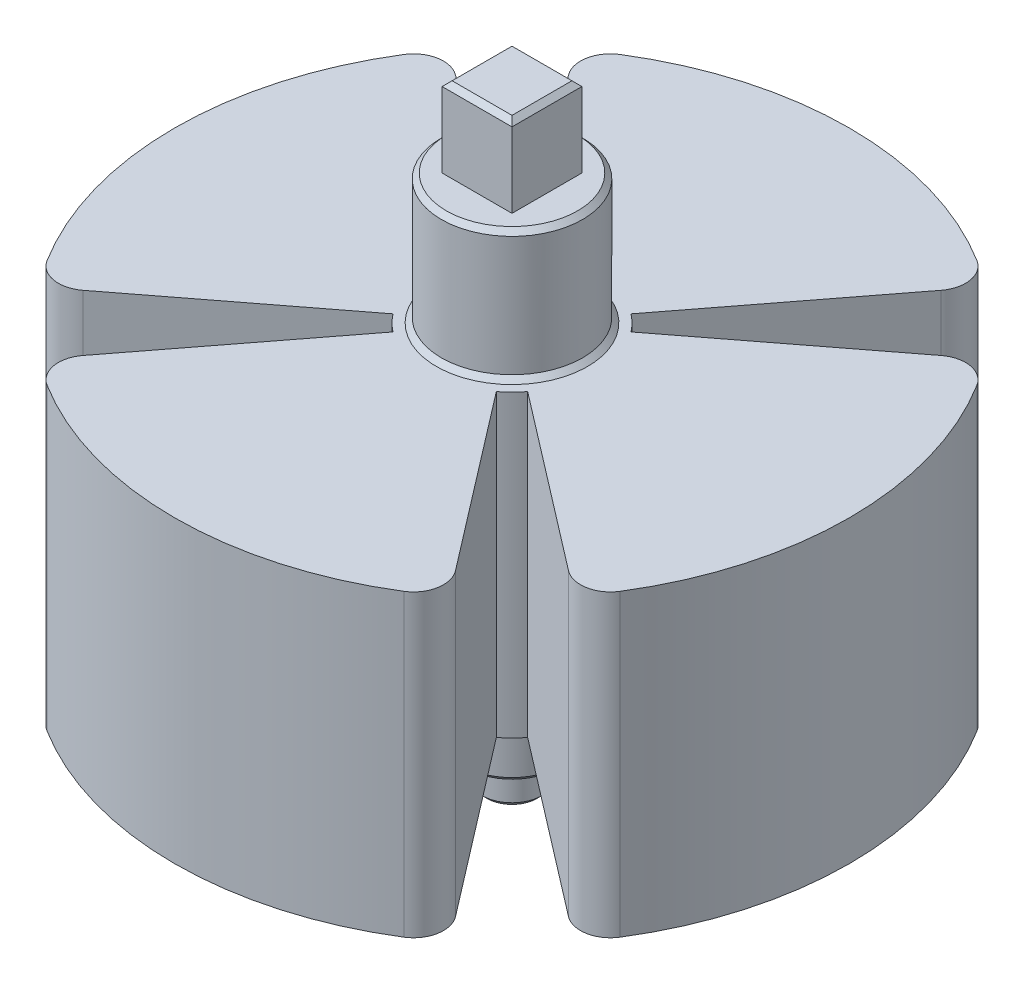
SolidWorks part; units mm, degrees
material "2024-O"
ref_plane "Front Plane" through (0, 0, 0) normal (0, 0, 1) x (1, 0, 0)
ref_plane "Top Plane" through (0, 0, 0) normal (0, 1, 0) x (1, 0, 0)
ref_plane "Right Plane" through (0, 0, 0) normal (1, 0, 0) x (0, 0, -1)
sketch "Sketch1" plane through (0, 0, 0) normal (0, 1, 0) x (1, 0, 0)
  line L0 (0, -1000) -> (0, 49000) construction
  line L1 (-9.4434, 18.6449) -> (1.2277, -4.2394)
  line L2 (10.4722, 2.3667) -> (15.7663, 13.7199)
  line L3 (18.6449, 9.4434) -> (-4.2394, -1.2277)
  line L4 (2.3667, -10.4722) -> (13.7199, -15.7663)
  line L5 (9.4434, -18.6449) -> (-1.2277, 4.2394)
  line L6 (-10.4722, -2.3667) -> (-15.7663, -13.7199)
  line L7 (-18.6449, -9.4434) -> (4.2394, 1.2277)
  line L8 (-2.3667, 10.4722) -> (-13.7199, 15.7663)
  line L10 (-1.75, 1.75) -> (1.75, 1.75)
  line L11 (-1.75, 1.75) -> (-1.75, -1.75)
  line L12 (-1.75, -1.75) -> (1.75, -1.75)
  line L13 (1.75, 1.75) -> (1.75, -1.75)
  line L14 (-1.75, 1.75) -> (1.75, -1.75) construction
  line L15 (-1.75, -1.75) -> (1.75, 1.75) construction
  circle A0 centre (0, 0) radius 20.9 construction
  arc A1 (-13.7199, 15.7663) -> (-18.6449, -9.4434) centre (0, 0) ccw
  circle A2 centre (0, 0) radius 17.15
  arc A3 (1.2277, -4.2394) -> (10.4722, 2.3667) centre (0, 7.25) ccw
  arc A4 (-4.2394, -1.2277) -> (2.3667, -10.4722) centre (7.25, 0) ccw
  arc A5 (-1.2277, 4.2394) -> (-10.4722, -2.3667) centre (0, -7.25) ccw
  arc A6 (4.2394, 1.2277) -> (-2.3667, 10.4722) centre (-7.25, 0) ccw
  arc A7 (-15.7663, -13.7199) -> (9.4434, -18.6449) centre (0, 0) ccw
  arc A8 (13.7199, -15.7663) -> (18.6449, 9.4434) centre (0, 0) ccw
  arc A9 (15.7663, 13.7199) -> (-9.4434, 18.6449) centre (0, 0) ccw
  circle A10 centre (0, 0) radius 3.5355
  point P29 (0, 0)
  dimension "D1" = 41.8
  dimension "D4" = 7.25
  dimension "D7" = 3.75
  dimension "D8" = 7.0711
  dimension "D2" = 25
  dimension "D3" = 25
  dimension "D6" = 3.5
  dimension "D5" = 4
extrude "Boss-Extrude1" add sketch "Sketch1" against normal blind 6.5 contours A10
extrude "Boss-Extrude2" add sketch "Sketch1<6>" along normal blind 4 contours L10 L13 L12 L11
sketch "Sketch1<6>" plane through (0, 0, 0) normal (0, 1, 0) x (1, 0, 0) same geometry as "Sketch1"
sketch "Sketch4" plane through (0, -6.5, 0) normal (0, -1, 0) x (1, 0, 0)
  circle A0 centre (0, 0) radius 4.25
  dimension "D1" = 8.5
extrude "Boss-Extrude5" add sketch "Sketch4" along normal blind 15 contours A0
sketch "Sketch2" plane through (0, -21.5, 0) normal (0, -1, 0) x (1, 0, 0)
  circle A0 centre (0, 0) radius 2.5
extrude "Boss-Extrude3" add sketch "Sketch2" along normal blind 3.2
sketch "Sketch3" plane through (0, -24.7, 0) normal (0, -1, 0) x (1, 0, 0)
  circle A0 centre (0, 0) radius 1.5
  dimension "D1" = 3
extrude "Boss-Extrude4" add sketch "Sketch3" along normal blind 1.8
sketch "Sketch5" plane through (0, -6.5, 0) normal (0, 1, 0) x (1, 0, 0)
  line L0 (-9.3303, 12.1595) -> (-1.19, 1.5509)
  line L1 (1.19, 1.5509) -> (9.3303, 12.1595)
  line L2 (0, -201000) -> (0, 249000) construction
  line L3 (12.1595, 9.3303) -> (1.5509, 1.19)
  line L4 (1.5509, -1.19) -> (12.1595, -9.3303)
  line L5 (9.3303, -12.1595) -> (1.19, -1.5509)
  line L6 (-1.19, -1.5509) -> (-9.3303, -12.1595)
  line L7 (-12.1595, -9.3303) -> (-1.5509, -1.19)
  line L8 (-1.5509, 1.19) -> (-12.1595, 9.3303)
  arc A0 (8.9332, 14.346) -> (-8.9332, 14.346) centre (0, 0) ccw
  circle A1 centre (0, 0) radius 17.15 construction
  arc A2 (9.3303, 12.1595) -> (8.9332, 14.346) centre (8.1403, 13.0727) ccw
  arc A3 (-9.3303, 12.1595) -> (-8.9332, 14.346) centre (-8.1403, 13.0727) cw
  arc A4 (-1.19, 1.5509) -> (1.19, 1.5509) centre (0, 2.464) ccw
  arc A5 (14.346, -8.9332) -> (14.346, 8.9332) centre (0, 0) ccw
  arc A6 (12.1595, -9.3303) -> (14.346, -8.9332) centre (13.0727, -8.1403) ccw
  arc A7 (12.1595, 9.3303) -> (14.346, 8.9332) centre (13.0727, 8.1403) cw
  arc A8 (1.5509, 1.19) -> (1.5509, -1.19) centre (2.464, 0) ccw
  arc A9 (-8.9332, -14.346) -> (8.9332, -14.346) centre (0, 0) ccw
  arc A10 (-9.3303, -12.1595) -> (-8.9332, -14.346) centre (-8.1403, -13.0727) ccw
  arc A11 (9.3303, -12.1595) -> (8.9332, -14.346) centre (8.1403, -13.0727) cw
  arc A12 (1.19, -1.5509) -> (-1.19, -1.5509) centre (0, -2.464) ccw
  arc A13 (-14.346, 8.9332) -> (-14.346, -8.9332) centre (0, 0) ccw
  arc A14 (-12.1595, 9.3303) -> (-14.346, 8.9332) centre (-13.0727, 8.1403) ccw
  arc A15 (-12.1595, -9.3303) -> (-14.346, -8.9332) centre (-13.0727, -8.1403) cw
  arc A16 (-1.5509, -1.19) -> (-1.5509, 1.19) centre (-2.464, 0) ccw
  point P45 (0, 0)
  dimension "D4" = 1.5
  dimension "D5" = 1.5
  dimension "D1" = 0.25
  dimension "D2" = 37.5
  dimension "D3" = 37.5
  dimension "D6" = 4
extrude "Boss-Extrude6" add sketch "Sketch5" against normal up to surface (15 mm away) up to face at (0, -21.5, -2.5)
chamfer "Chamfer1" distance 0.25 angle 45 10 edges at (0, 4, -1.75) (1.75, 4, 0) (0, 4, 1.75) (-1.75, 4, 0) (0, 0, 3.5355) (0, -24.7, -1.5) (0, -26.5, -1.5) (0, -21.5, -2.5) (0, -24.7, -2.5) (0, -6.5, -3.5355)
equation "\"D2@Sketch5\"=\"D3@Sketch5\""
